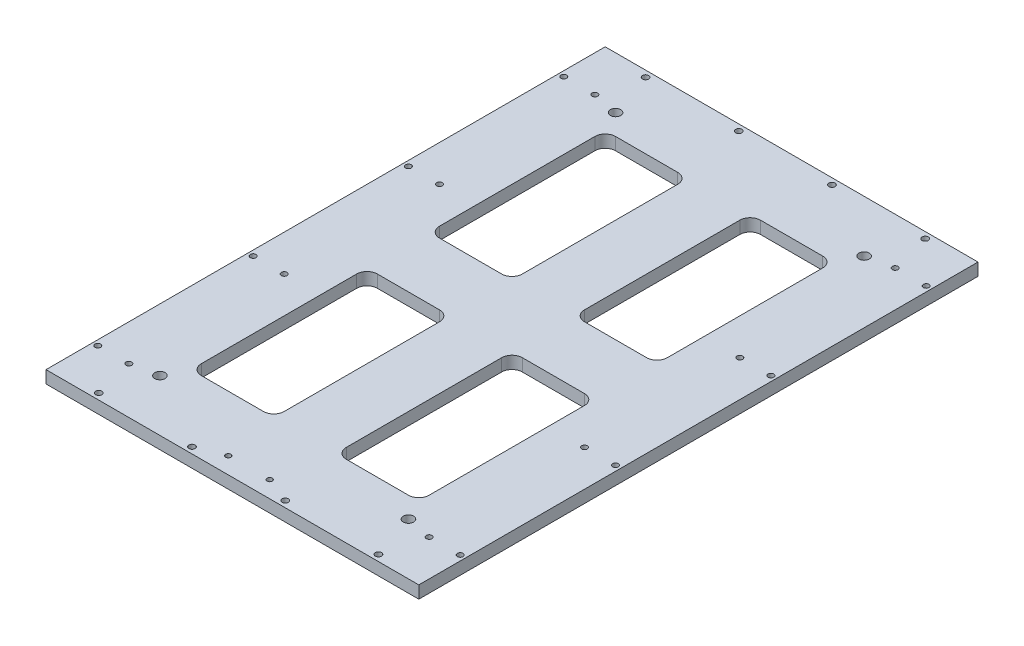
SolidWorks part; units mm, degrees
material "HDPE-green"
ref_plane "Front Plane" through (0, 0, 0) normal (0, 0, 1) x (1, 0, 0)
ref_plane "Top Plane" through (0, 0, 0) normal (0, 1, 0) x (1, 0, 0)
ref_plane "Right Plane" through (0, 0, 0) normal (1, 0, 0) x (0, 0, -1)
sketch "Sketch1" plane through (0, 0, 0) normal (0, 1, 0) x (1, 0, 0)
  line L1 (-180, -270) -> (180, -270)
  line L2 (-180, -270) -> (-180, 270)
  line L3 (-180, 270) -> (180, 270)
  line L4 (180, -270) -> (180, 270)
  line L5 (-180, -270) -> (180, 270) construction
  line L6 (-180, 270) -> (180, -270) construction
  point P0 (0, 0)
extrude "Boss-Extrude1" add sketch "Sketch1" along normal blind 12
sketch "Sketch3" plane through (0, 0, 0) normal (0, -1, 0) x (1, 0, 0)
  line L0 (-207.4551, 264) -> (223.7581, 264) construction
  line L1 (-180, 270) -> (180, 270) construction
  line L2 (180, 270) -> (180, -270) construction
  circle A0 centre (135, 264) radius 3
  dimension "D2" = 6
  dimension "D3" = 45
  dimension "D1" = 6
extrude "Cut-Extrude2" cut sketch "Sketch3" against normal up to next
pattern_linear "LPattern1" count 4 spacing 90 along (-1, 0, 0) of "Cut-Extrude2"
mirror "Mirror1" about plane through (0, 0, 0) normal (0, 0, 1) of "LPattern1"
sketch "Sketch4" plane through (0, 12, 0) normal (0, 1, 0) x (1, 0, 0)
  line L0 (-160, 299.1839) -> (-160, -309.0635) construction
  line L1 (-180, 270) -> (-180, -270) construction
  line L2 (-188.5351, 0) -> (-124.846, 0) construction
  line L3 (-188.5351, 225) -> (-124.846, 225) construction
  line L4 (-129.91, -225) -> (-208.5429, -225) construction
  circle A0 centre (-175, 225) radius 2.75
  circle A1 centre (-145, 225) radius 2.75
  dimension "D4" = 5.5
  dimension "D5" = 5.5
  dimension "D7" = 15
  dimension "D1" = 20
  dimension "D2" = 225
  dimension "D3" = 225
  dimension "D6" = 15
extrude "Cut-Extrude3" cut sketch "Sketch4" against normal up to next
pattern_linear "LPattern2" count 4 spacing 150 along (0, 0, 1) of "Cut-Extrude3"
mirror "Mirror2" about plane through (0, 0, 0) normal (1, 0, 0) of "LPattern2"
sketch "Sketch7" plane through (0, 0, 0) normal (0, -1, 0) x (1, 0, 0)
  line L0 (180, -270) -> (-180, -270) construction
  line L1 (-40, -30) -> (-100, -30)
  line L2 (-30, -40) -> (-30, -190)
  line L3 (-40, -200) -> (-100, -200)
  line L4 (-110, -40) -> (-110, -190)
  line L5 (-30, -30) -> (-110, -200) construction
  line L6 (-30, -200) -> (-110, -30) construction
  line L7 (-180, -270) -> (-180, 270) construction
  arc A0 (-100, -30) -> (-110, -40) centre (-100, -40) ccw
  arc A1 (-40, -30) -> (-30, -40) centre (-40, -40) cw
  arc A2 (-30, -190) -> (-40, -200) centre (-40, -190) cw
  arc A3 (-100, -200) -> (-110, -190) centre (-100, -190) cw
  point P0 (-70, -115)
  dimension "D5" = 10
  dimension "D1" = 70
  dimension "D2" = 30
  dimension "D3" = 30
  dimension "D4" = 70
extrude "Cut-Extrude5" cut sketch "Sketch7" against normal up to next
mirror "Mirror5" about plane through (0, 0, 0) normal (1, 0, 0) of "Cut-Extrude5"
mirror "Mirror6" about plane through (0, 0, 0) normal (0, 0, 1) of "Mirror5"
hole_wizard "Ø10.0 (10) Diameter Hole1" positions "Sketch9" profile "Sketch8" hole size "Ø10.0" standard "ISO" end condition up to next
sketch "Sketch9" plane through (0, 0, 0) normal (0, -1, 0) x (1, 0, 0)
  point P0 (-120, -220)
  dimension "D1" = 220
  dimension "D2" = 120
sketch "Sketch8" plane through (-120, 0, -220) normal (1, 0, 0) x (0, 0, -1)
  line L0 (0, 0) -> (0, 12.001)
  line L1 (0, 12.001) -> (5, 12.001)
  line L2 (5, 12.001) -> (5, 0)
  line L5 (5, 0) -> (0, 0)
  line L11 (0, -6.35) -> (0, 107.95) construction
  dimension "Thru Hole Dia." = 10
  dimension "Thru Hole Depth" = 12.001
mirror "Mirror7" about plane through (0, 0, 0) normal (1, 0, 0) of "Ø10.0 (10) Diameter Hole1"
mirror "Mirror8" about plane through (0, 0, 0) normal (0, 0, 1) of "Mirror7"
hole_wizard "Ø5.0 (5) Diameter Hole1" positions "Sketch11" profile "Sketch12" hole size "Ø5.0" standard "ISO" end condition up to next
sketch "Sketch11" plane through (0, 12, 0) normal (0, 1, 0) x (-1, 0, 0)
  line L0 (180, 270) -> (-180, 270) construction
  point P0 (20, 254)
  point P1 (-20, 254)
  dimension "D1" = 20
  dimension "D2" = 20
  dimension "D3" = 16
  dimension "D4" = 16
sketch "Sketch12" plane through (-20, 12, 254) normal (1, 0, 0) x (0, 0, 1)
  line L0 (0, 0) -> (0, 12)
  line L1 (0, 12) -> (2.5, 12)
  line L2 (2.5, 12) -> (2.5, 0)
  line L5 (2.5, 0) -> (0, 0)
  line L11 (0, -6.35) -> (0, 107.95) construction
  dimension "Thru Hole Dia." = 5
  dimension "Thru Hole Depth" = 12
